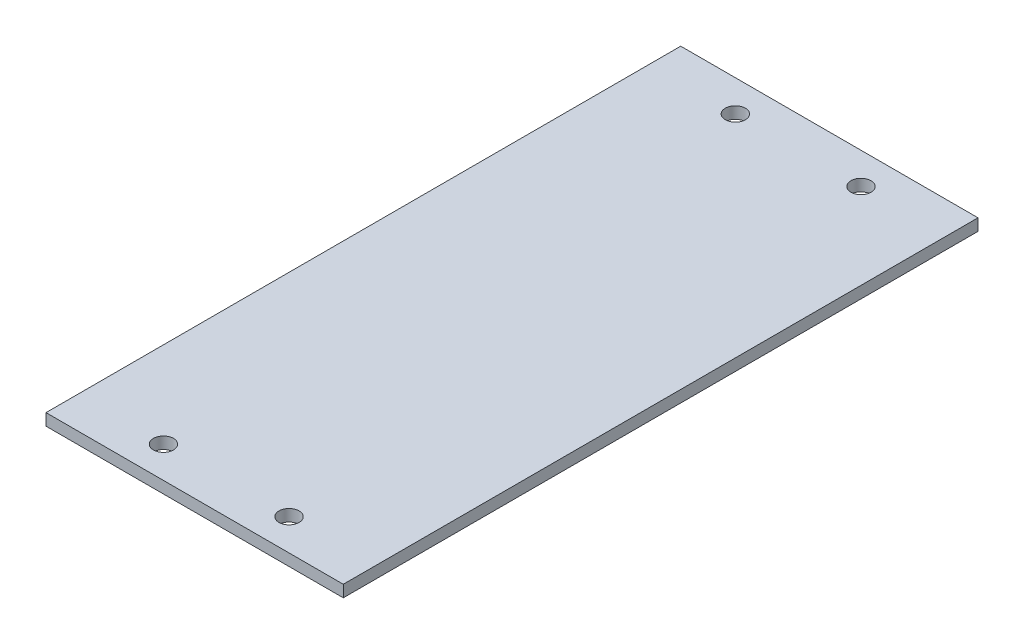
SolidWorks part; units mm, degrees
material "Balsa"
ref_plane "Front Plane" through (0, 0, 0) normal (0, 0, 1) x (1, 0, 0)
ref_plane "Top Plane" through (0, 0, 0) normal (0, 1, 0) x (1, 0, 0)
ref_plane "Right Plane" through (0, 0, 0) normal (1, 0, 0) x (0, 0, -1)
sketch "Sketch1" plane through (0, 0, 0) normal (0, 1, 0) x (1, 0, 0)
  line L0 (-152.4, 304.8) -> (152.4, 304.8) construction
  line L1 (152.4, 304.8) -> (152.4, -304.8) construction
  line L2 (0, 304.8) -> (0, 0) construction
  line L3 (0, 0) -> (152.4, 0) construction
  dimension "Width" = 304.8
  dimension "Length" = 609.6
sketch "Sketch2" plane through (0, 0, 0) normal (1, 0, 0) x (0, 0, -1)
  line L0 (304.8, 0) -> (304.8, -9.525) construction
  dimension "Thk" = 9.525
sketch "Sketch3" plane through (0, 0, 0) normal (0, 1, 0) x (1, 0, 0)
  line L1 (-152.4, 304.8) -> (152.4, 304.8)
  line L2 (-152.4, 304.8) -> (-152.4, -304.8)
  line L3 (-152.4, -304.8) -> (152.4, -304.8)
  line L4 (152.4, 304.8) -> (152.4, -304.8)
extrude "Boss-Extrude1" add sketch "Sketch3" against normal up to vertex (9.525 mm away) up to point (0, -9.525, -304.8)
sketch "Sketch4" plane through (0, 0, 0) normal (0, 1, 0) x (1, 0, 0)
  line L0 (152.4, -304.8) -> (152.4, 304.8) construction
  line L1 (-152.4, 304.8) -> (152.4, 304.8)
  line L2 (-152.4, 304.8) -> (-152.4, 208.661)
  line L3 (-120.245, 208.661) -> (120.245, 208.661)
  line L4 (152.4, 304.8) -> (152.4, 208.661)
  line L5 (-152.4, -304.8) -> (152.4, -304.8) construction
  line L6 (0, 0) -> (0, 208.661) construction
  line L8 (-152.4, 208.661) -> (-152.4, -304.8)
  line L9 (-152.4, -304.8) -> (-120.245, -304.8)
  line L10 (-120.245, 208.661) -> (-120.245, -304.8)
  line L11 (152.4, 208.661) -> (152.4, -304.8)
  line L12 (120.245, 208.661) -> (120.245, -304.8)
  line L13 (152.4, -304.8) -> (120.245, -304.8)
  dimension "D1" = 513.461
  dimension "D2" = 32.155
  dimension "D3" = 32.155
extrude "Cut-Extrude1" cut sketch "Sketch4" against normal blind 15.24 contours L2 L8 L9 L10 L3 L12 L13 L11 L4 L1
sketch "Sketch5" plane through (0, 0, 0) normal (0, 1, 0) x (1, 0, 0)
  line L1 (-50.8, -109.22) -> (50.8, -109.22)
  line L2 (-57.15, -102.87) -> (-57.15, -20.32)
  line L3 (-50.8, -13.97) -> (50.8, -13.97)
  line L4 (57.15, -102.87) -> (57.15, -20.32)
  line L5 (-57.15, -109.22) -> (57.15, -13.97) construction
  line L6 (-57.15, -13.97) -> (57.15, -109.22) construction
  arc A0 (-50.8, -109.22) -> (-57.15, -102.87) centre (-50.8, -102.87) cw
  arc A1 (50.8, -109.22) -> (57.15, -102.87) centre (50.8, -102.87) ccw
  arc A2 (50.8, -13.97) -> (57.15, -20.32) centre (50.8, -20.32) cw
  arc A3 (-57.15, -20.32) -> (-50.8, -13.97) centre (-50.8, -20.32) cw
  point P0 (0, -61.595)
  dimension "D4" = 6.35
  dimension "D1" = 95.25
  dimension "D2" = 61.595
  dimension "D3" = 114.3
extrude "Cut-Extrude2" [suppressed] cut sketch "Sketch5" against normal blind 12.7
sketch "Sketch9" plane through (0, -9.525, 0) normal (0, -1, 0) x (-1, 0, 0)
  line L0 (101.442, 208.661) -> (-101.7753, 208.661) construction
  line L1 (120.245, 208.661) -> (-120.245, 208.661) construction
  line L2 (-0.1667, 208.661) -> (-0.1667, 141.8706) construction
  line L3 (-101.7753, 208.661) -> (-101.6, -304.8) construction
  line L4 (120.245, -304.8) -> (-120.245, -304.8) construction
  line L5 (-101.6, -304.8) -> (-101.6877, -48.0695) construction
  line L6 (-101.6877, -48.0695) -> (101.6, -48.0695) construction
  line L7 (50.6333, 208.661) -> (-0.1667, 208.661) construction
  line L8 (-0.1667, 208.661) -> (-50.9667, 208.661) construction
  line L9 (50.6333, 208.661) -> (50.6333, 183.261) construction
  line L10 (50.6333, 183.261) -> (-50.9667, 183.261) construction
  line L11 (-50.9667, 183.261) -> (-50.9667, 208.661) construction
  line L12 (-0.1667, 141.8706) -> (-3.0721, -304.8) construction
  circle A0 centre (-50.9667, 183.261) radius 8.128
  circle A2 centre (50.6333, 183.261) radius 8.128
  circle A5 centre (50.6333, -279.4) radius 8.128
  circle A6 centre (-50.9667, -279.4) radius 8.128
  dimension "D3" = 25.4
  dimension "D1" = 16.256
  dimension "D2" = 50.8
  dimension "D4" = 50.8
extrude "Cut-Extrude3" cut sketch "Sketch9" against normal through all
